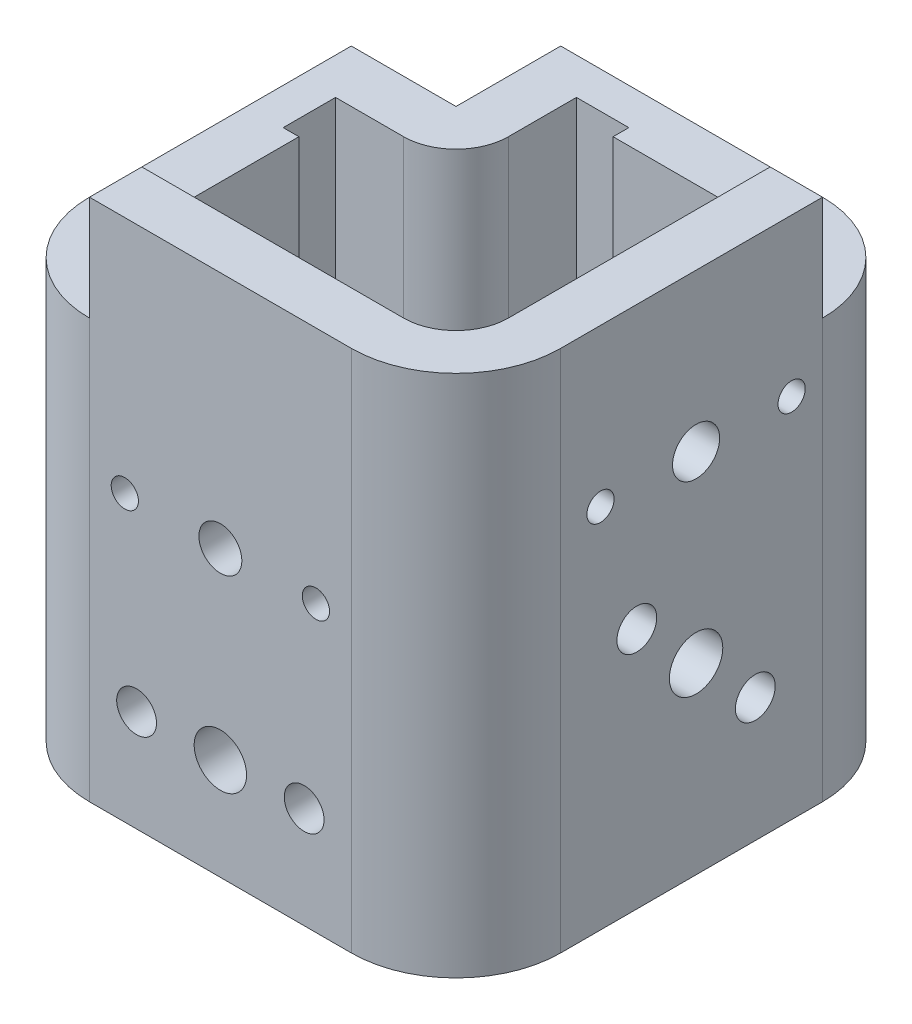
SolidWorks part; units mm, degrees
material "ABS"
ref_plane "Front Plane" through (0, 0, 0) normal (0, 0, 1) x (1, 0, 0)
ref_plane "Top Plane" through (0, 0, 0) normal (0, 1, 0) x (1, 0, 0)
ref_plane "Right Plane" through (0, 0, 0) normal (1, 0, 0) x (0, 0, -1)
sketch "Sketch1" plane through (0, 0, 0) normal (0, 1, 0) x (1, 0, 0)
  line L1 (-25, 35) -> (25, 35)
  line L2 (-35, 25) -> (-35, -25)
  line L3 (-25, -35) -> (25, -35)
  line L4 (35, 25) -> (35, -25)
  line L5 (-25, -25) -> (25, 25) construction
  line L6 (-25, 25) -> (25, -25) construction
  line L7 (-25, 45) -> (25, 45)
  line L8 (45, 25) -> (45, -25)
  line L9 (-25, -45) -> (25, -45)
  line L10 (-45, 25) -> (-45, -25)
  arc A0 (35, 25) -> (25, 35) centre (25, 25) ccw
  arc A1 (25, -35) -> (35, -25) centre (25, -25) ccw
  arc A2 (-35, -25) -> (-25, -35) centre (-25, -25) ccw
  arc A3 (-35, 25) -> (-25, 35) centre (-25, 25) cw
  arc A5 (45, 25) -> (25, 45) centre (25, 25) ccw
  arc A6 (25, -45) -> (45, -25) centre (25, -25) ccw
  arc A7 (-45, -25) -> (-25, -45) centre (-25, -25) ccw
  arc A8 (-45, 25) -> (-25, 45) centre (-25, 25) cw
  point P12 (0, 0)
  dimension "D1" = 10
  dimension "D3" = 10
  dimension "D2" = 70
extrude "Boss-Extrude1" add sketch "Sketch1" along normal blind 30 and the other way blind 70
sketch "Sketch2" plane through (45, 0, 0) normal (1, 0, 0) x (0, 0, -1)
  arc A2 (21.6984, 0) -> (16.4984, 0) centre (19.0984, 0) ccw construction
  circle A3 centre (0.8484, 0) radius 4.5 construction
  circle A4 centre (0.8484, -35) radius 5.1 construction
  circle A5 centre (0.8484, 0) radius 4.5
  circle A6 centre (0.8484, -35) radius 5.1
  arc A7 (16.4984, 0) -> (21.6984, 0) centre (19.0984, 0) ccw construction
  arc A8 (-14.8016, 0) -> (-20.0016, 0) centre (-17.4016, 0) ccw construction
  arc A9 (-20.0016, 0) -> (-14.8016, 0) centre (-17.4016, 0) ccw construction
  arc A10 (21.6984, 0) -> (16.4984, 0) centre (19.0984, 0) ccw
  arc A11 (16.4984, 0) -> (21.6984, 0) centre (19.0984, 0) ccw
  arc A12 (-14.8016, 0) -> (-20.0016, 0) centre (-17.4016, 0) ccw
  arc A13 (-20.0016, 0) -> (-14.8016, 0) centre (-17.4016, 0) ccw
  circle A14 centre (12.1622, -46.3137) radius 3.8 construction
  circle A15 centre (-10.4653, -23.6863) radius 3.8 construction
  circle A16 centre (12.1622, -46.3137) radius 3.8
  circle A17 centre (-10.4653, -23.6863) radius 3.8
extrude "Cut-Extrude1" cut sketch "Sketch2" against normal up to next
sketch "Sketch5" plane through (45, 0, 0) normal (1, 0, 0) x (0, 0, -1)
  line L0 (25, 30) -> (25, -70) construction
  line L1 (25, 10) -> (45, 10)
  line L2 (25, 10) -> (25, 30)
  line L3 (25, 30) -> (45, 30)
  line L4 (45, 10) -> (45, 30)
  line L5 (-25, 30) -> (25, 30) construction
  line L6 (45, 30) -> (45, -70) construction
  dimension "D1" = 20
extrude "Cut-Extrude2" cut sketch "Sketch5" against normal through all
sketch "Sketch7" plane through (0, 0, 45) normal (0, 0, 1) x (1, 0, 0)
  line L0 (-25, -70) -> (-25, 30) construction
  line L1 (-25, 10) -> (-45, 10)
  line L2 (-25, 10) -> (-25, 30)
  line L3 (-25, 30) -> (-45, 30)
  line L4 (-45, 10) -> (-45, 30)
  line L5 (-25, 30) -> (25, 30) construction
  line L6 (-45, -70) -> (-45, 30) construction
  dimension "D1" = 20
extrude "Cut-Extrude3" cut sketch "Sketch7" against normal up to next
sketch "Sketch8" plane through (0, 0, 45) normal (0, 0, 1) x (1, 0, 0)
  line L0 (0, 30) -> (0, -70) construction
  line L1 (-25, 30) -> (25, 30) construction
  line L2 (-25, -70) -> (25, -70) construction
  circle A0 centre (685, -50.6) radius 5 construction
  circle A1 centre (685, -15.6) radius 5 construction
  circle A2 centre (685, -50.6) radius 5
  circle A3 centre (685, -15.6) radius 5
  circle A4 centre (0, -15.6) radius 4.1
  circle A5 centre (0, -50.6) radius 5
  circle A7 centre (685, -50.6) radius 5 construction
  circle A8 centre (-16, -50.6) radius 3.8 construction
  circle A9 centre (16, -50.6) radius 3.8 construction
  circle A10 centre (-16, -50.6) radius 3.8
  circle A11 centre (16, -50.6) radius 3.8
  arc A12 (-15.65, -15.6) -> (-20.85, -15.6) centre (-18.25, -15.6) ccw construction
  arc A13 (-20.85, -15.6) -> (-15.65, -15.6) centre (-18.25, -15.6) ccw construction
  arc A14 (20.85, -15.6) -> (15.65, -15.6) centre (18.25, -15.6) ccw construction
  arc A15 (15.65, -15.6) -> (20.85, -15.6) centre (18.25, -15.6) ccw construction
  arc A16 (-15.65, -15.6) -> (-20.85, -15.6) centre (-18.25, -15.6) ccw
  arc A17 (-20.85, -15.6) -> (-15.65, -15.6) centre (-18.25, -15.6) ccw
  arc A18 (20.85, -15.6) -> (15.65, -15.6) centre (18.25, -15.6) ccw
  arc A19 (15.65, -15.6) -> (20.85, -15.6) centre (18.25, -15.6) ccw
  point P10 (0, 0)
  point P12 (0, -15.6)
  point P14 (0, -43.5987)
  dimension "D1" = 8.2
extrude "Cut-Extrude6" cut sketch "Sketch8" against normal up to surface (10 mm away) up to face at (-5, -14, 35)
sketch "Sketch9" plane through (0, 10, 0) normal (0, 1, 0) x (1, 0, 0)
  line L0 (-45, 25) -> (-45, -25) construction
  line L1 (-25, 45) -> (25, 45) construction
  line L2 (-25, 25) -> (-45, 25)
  line L3 (-25, 25) -> (-25, 45)
  line L4 (-25, 45) -> (-45, 45)
  line L5 (-45, 25) -> (-45, 45)
  line L6 (720, 4.9984) -> (723, 4.9984) construction
  line L7 (-35, 25) -> (-38, 25)
  line L8 (-35, 25) -> (-35, 5)
  line L9 (-35, 5) -> (-38, 5)
  line L10 (-38, 25) -> (-38, 5)
  line L11 (-25, 35) -> (-5, 35)
  line L12 (-25, 35) -> (-25, 38)
  line L13 (-25, 38) -> (-5, 38)
  line L14 (-5, 35) -> (-5, 38)
  line L16 (-35, -25) -> (-35, 25) construction
  point P19 (0, 0)
  point P20 (0, 0)
  point P21 (-37.1768, 23.5559)
  point P22 (0, 0)
  point P23 (0, 0)
  point P24 (0, 0)
  point P27 (-59.9999, 32.0241)
  arc M5 (-25, 45) -> (-45, 25) centre (-25, 25) ccw
  line M6 (-45, 25) -> (-45, -25)
  line M10 (-35, -25) -> (-35, 25)
  arc M11 (-35, 25) -> (-25, 35) centre (-25, 25) cw
  line M12 (-25, 35) -> (25, 35)
  line M16 (25, 45) -> (-25, 45)
  dimension "D1" = 20
  dimension "D2" = 20
extrude "Cut-Extrude7" cut sketch "Sketch9" against normal through all contours L2 L10 L9 M10 | L10 L7 L3 L2 M11 M12 M16 M5 M6 | L14 L13 L3 M12 region at (-36.5, 10, -15) region at (-34.903, 10, -34.903) region at (-15, 10, -36.5)
sketch "Sketch10" plane through (0, 10, 0) normal (0, 1, 0) x (1, 0, 0)
  line L0 (-25, 45) -> (-25, 25)
  line L1 (-45, 25) -> (-25, 25)
  line L3 (-45, 15) -> (-25, 15)
  line L4 (-15, 45) -> (-15, 25)
  line L5 (-45, 15) -> (-15, 15) construction
  line L6 (-15, 45) -> (-15, 15) construction
  line L7 (-45, 25) -> (-25, 25) construction
  line L8 (-45, 25) -> (-45, -25) construction
  line L9 (-25, 45) -> (-25, 25) construction
  line L10 (-25, 45) -> (25, 45) construction
  line L11 (-15, 45) -> (-25, 45)
  line L12 (-45, 25) -> (-45, 15)
  arc A0 (-25, 15) -> (-15, 25) centre (-25, 25) ccw
  dimension "D2" = 10
  dimension "D1" = 10
extrude "Boss-Extrude2" add sketch "Sketch10" against normal up to surface (80 mm away) up to face at (-3.9893, -70, -3.9893)
